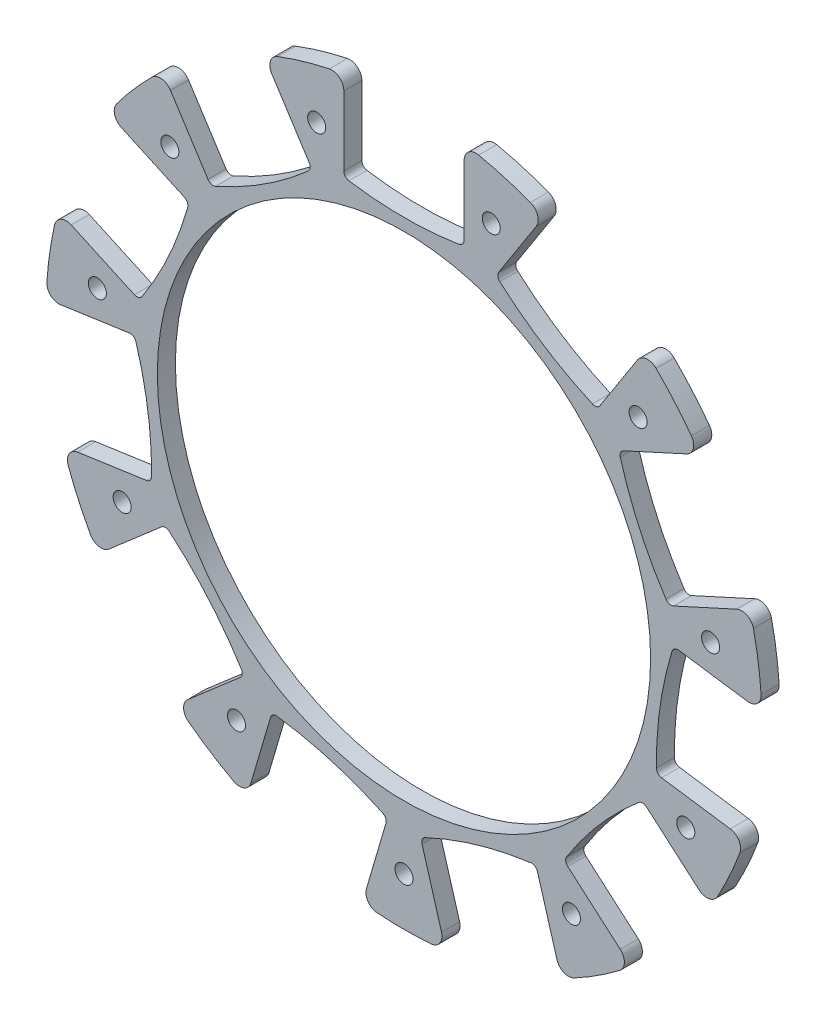
SolidWorks part; units mm, degrees
material "Thornel Mat VMA"
ref_plane "前视基准面" through (0, 0, 0) normal (0, 0, 1) x (1, 0, 0)
ref_plane "上视基准面" through (0, 0, 0) normal (0, 1, 0) x (1, 0, 0)
ref_plane "右视基准面" through (0, 0, 0) normal (1, 0, 0) x (0, 0, -1)
sketch "草图2" plane through (0, 0, 0) normal (0, 0, 1) x (1, 0, 0)
  line L0 (12.85, 52.4) -> (12.85, 55.6) construction
  line L1 (12.85, 55.6) -> (10, 55.6) construction
  line L2 (10, 52.4) -> (12.85, 52.4) construction
  line L3 (9.35, 50.9) -> (10, 50.9) construction
  line L4 (10, 50.9) -> (10, 57.1) construction
  line L5 (10, 57.1) -> (9.35, 57.1) construction
  line L6 (9.35, 46.1078) -> (9.35, 61.8922) construction
  line L7 (8.4948, 45.1184) -> (8.4948, 62.8816) construction
  line L8 (-8.4948, 62.8816) -> (-8.4948, 45.1184) construction
  line L9 (-9.35, 61.8922) -> (-9.35, 46.1078) construction
  line L10 (-10, 50.9) -> (-9.35, 50.9) construction
  line L11 (-9.35, 57.1) -> (-10, 57.1) construction
  line L12 (-10, 57.1) -> (-10, 50.9) construction
  line L13 (-10, 55.6) -> (-12.85, 55.6) construction
  line L14 (-12.85, 52.4) -> (-10, 52.4) construction
  line L15 (-12.85, 55.6) -> (-12.85, 52.4) construction
  line L16 (-8.4948, 54) -> (8.4948, 54) construction
  line L17 (10, 58.6536) -> (10, 43.8392)
  line L18 (-10, 58.6536) -> (-10, 43.8392)
  line L19 (40.1231, 43.9362) -> (32.1138, 31.4735)
  line L20 (23.298, 54.749) -> (15.2887, 42.2863)
  line L21 (57.5074, 15.2693) -> (44.0317, 9.1151)
  line L22 (49.1991, 33.4619) -> (35.7234, 27.3078)
  line L23 (56.6335, -18.2455) -> (41.9698, -16.1372)
  line L24 (59.4798, 1.5509) -> (44.8161, 3.6592)
  line L25 (37.7789, -45.9675) -> (26.5829, -36.2661)
  line L26 (50.8761, -30.8525) -> (39.6801, -21.1511)
  line L27 (6.9297, -59.0951) -> (2.756, -44.8807)
  line L28 (26.1196, -53.4604) -> (21.9459, -39.2461)
  line L29 (-26.1196, -53.4604) -> (-21.9459, -39.2461)
  line L30 (-6.9297, -59.0951) -> (-2.756, -44.8807)
  line L31 (-50.8761, -30.8525) -> (-39.6801, -21.1511)
  line L32 (-37.7789, -45.9675) -> (-26.5829, -36.2661)
  line L33 (-59.4798, 1.5509) -> (-44.8161, 3.6592)
  line L34 (-56.6335, -18.2455) -> (-41.9698, -16.1372)
  line L35 (-49.1991, 33.4619) -> (-35.7234, 27.3078)
  line L36 (-57.5074, 15.2693) -> (-44.0317, 9.1151)
  line L37 (-23.298, 54.749) -> (-15.2887, 42.2863)
  line L38 (-40.1231, 43.9362) -> (-32.1138, 31.4735)
  line L39 (0, 44.5) -> (0, 43) construction
  arc A0 (9.35, 61.8922) -> (8.4948, 62.8816) centre (8.35, 61.8922) ccw construction
  arc A1 (8.4948, 45.1184) -> (9.35, 46.1078) centre (8.35, 46.1078) ccw construction
  arc A2 (-8.4948, 45.1184) -> (8.4948, 45.1184) centre (0, 103.1567) ccw construction
  arc A3 (8.4948, 62.8816) -> (-8.4948, 62.8816) centre (0, 4.8433) ccw construction
  arc A4 (-8.4948, 62.8816) -> (-9.35, 61.8922) centre (-8.35, 61.8922) ccw construction
  arc A5 (-9.35, 46.1078) -> (-8.4948, 45.1184) centre (-8.35, 46.1078) ccw construction
  circle A6 centre (0, 0) radius 59.5 construction
  arc A7 (-10, 43.8392) -> (10, 43.8392) centre (0, 103) ccw
  arc A8 (15.2887, 42.2863) -> (32.1138, 31.4735) centre (55.686, 86.6491) ccw
  arc A9 (35.7234, 27.3078) -> (44.0317, 9.1151) centre (93.6921, 42.7877) ccw
  arc A10 (44.8161, 3.6592) -> (41.9698, -16.1372) centre (101.9516, -14.6584) ccw
  arc A11 (39.6801, -21.1511) -> (26.5829, -36.2661) centre (77.8422, -67.4507) ccw
  arc A12 (21.9459, -39.2461) -> (2.756, -44.8807) centre (29.0185, -98.8278) ccw
  arc A13 (-2.756, -44.8807) -> (-21.9459, -39.2461) centre (-29.0185, -98.8278) ccw
  arc A14 (-26.5829, -36.2661) -> (-39.6801, -21.1511) centre (-77.8422, -67.4507) ccw
  arc A15 (-41.9698, -16.1372) -> (-44.8161, 3.6592) centre (-101.9516, -14.6584) ccw
  arc A16 (-44.0317, 9.1151) -> (-35.7234, 27.3078) centre (-93.6921, 42.7877) ccw
  arc A17 (-32.1138, 31.4735) -> (-15.2887, 42.2863) centre (-55.686, 86.6491) ccw
  arc A18 (-23.298, 54.749) -> (-10, 58.6536) centre (0, 0) cw
  arc A19 (10, 58.6536) -> (23.298, 54.749) centre (0, 0) cw
  arc A20 (40.1231, 43.9362) -> (49.1991, 33.4619) centre (0, 0) cw
  arc A21 (57.5074, 15.2693) -> (59.4798, 1.5509) centre (0, 0) cw
  arc A22 (56.6335, -18.2455) -> (50.8761, -30.8525) centre (0, 0) cw
  arc A23 (37.7789, -45.9675) -> (26.1196, -53.4604) centre (0, 0) cw
  arc A24 (6.9297, -59.0951) -> (-6.9297, -59.0951) centre (0, 0) cw
  arc A25 (-49.1991, 33.4619) -> (-40.1231, 43.9362) centre (0, 0) cw
  arc A26 (-57.5074, 15.2693) -> (-59.4798, 1.5509) centre (0, 0) ccw
  arc A27 (-56.6335, -18.2455) -> (-50.8761, -30.8525) centre (0, 0) ccw
  arc A28 (-37.7789, -45.9675) -> (-26.1196, -53.4604) centre (0, 0) ccw
  circle A29 centre (0, 0) radius 63.5 construction
  circle A30 centre (0, 0) radius 41
  circle A31 centre (0, -51.5) radius 1.5
  circle A32 centre (-27.843, -43.3246) radius 1.5
  circle A33 centre (-46.846, -21.3939) radius 1.5
  circle A34 centre (-50.9758, 7.3292) radius 1.5
  circle A35 centre (-38.9211, 33.7253) radius 1.5
  circle A36 centre (-14.5092, 49.4139) radius 1.5
  circle A37 centre (14.5092, 49.4139) radius 1.5
  circle A38 centre (38.9211, 33.7253) radius 1.5
  circle A39 centre (50.9758, 7.3292) radius 1.5
  circle A40 centre (46.846, -21.3939) radius 1.5
  circle A41 centre (27.843, -43.3246) radius 1.5
  point P37 (-12.85, 54)
  point P41 (-9.675, 57.1)
  point P42 (-9.675, 50.9)
  point P43 (0, 63.5)
  point P44 (0, 44.5)
  point P45 (-10, 54)
  point P46 (-9.35, 54)
  point P47 (9.35, 54)
  point P48 (10, 54)
  point P49 (12.85, 54)
  point P54 (0, 54)
  point P108 (0, 0)
  point P132 (0, 0)
  dimension "D1" = 25.7
  dimension "D8" = 1
  dimension "D9" = 58.6567
  dimension "D11" = 119
  dimension "D12" = 60
  dimension "D15" = 127
  dimension "D16" = 82
  dimension "D17" = 3
  dimension "D2" = 3.2
  dimension "D3" = 6.2
  dimension "D4" = 20
  dimension "D5" = 19
  dimension "D6" = 18.7
  dimension "D7" = 54
  dimension "D10" = 16.9896
  dimension "D13" = 1.5
  dimension "D18" = 51.5
  dimension "D14" = 11
  dimension "D19" = 11
extrude "凸台-拉伸1" add sketch "草图2" along normal blind 3
fillet "圆角1" radius 1 22 edges at (10, 43.8392, 1.5) (-10, 43.8392, 1.5) (-15.2887, 42.2863, 1.5) (-32.1138, 31.4735, 1.5) (-35.7234, 27.3078, 1.5) (-44.0317, 9.1151, 1.5) (-44.8161, 3.6592, 1.5) (-41.9698, -16.1372, 1.5) (-39.6801, -21.1511, 1.5) (-26.5829, -36.2661, 1.5) (-21.9459, -39.2461, 1.5) (-2.756, -44.8807, 1.5) (2.756, -44.8807, 1.5) (21.9459, -39.2461, 1.5) (26.5829, -36.2661, 1.5) (39.6801, -21.1511, 1.5) (41.9698, -16.1372, 1.5) (44.8161, 3.6592, 1.5) (44.0317, 9.1151, 1.5) (35.7234, 27.3078, 1.5) (32.1138, 31.4735, 1.5) (15.2887, 42.2863, 1.5)
fillet "圆角2" radius 2 22 edges at (10, 58.6536, 1.5) (-10, 58.6536, 1.5) (-23.298, 54.749, 1.5) (-40.1231, 43.9362, 1.5) (-49.1991, 33.4619, 1.5) (-57.5074, 15.2693, 1.5) (-59.4798, 1.5509, 1.5) (-56.6335, -18.2455, 1.5) (-50.8761, -30.8525, 1.5) (-37.7789, -45.9675, 1.5) (-26.1196, -53.4604, 1.5) (-6.9297, -59.0951, 1.5) (6.9297, -59.0951, 1.5) (26.1196, -53.4604, 1.5) (37.7789, -45.9675, 1.5) (50.8761, -30.8525, 1.5) (56.6335, -18.2455, 1.5) (59.4798, 1.5509, 1.5) (57.5074, 15.2693, 1.5) (49.1991, 33.4619, 1.5) (40.1231, 43.9362, 1.5) (23.298, 54.749, 1.5)
ref_axis "基准轴1" through (0, 0, 3) along (0, 0, -1)
